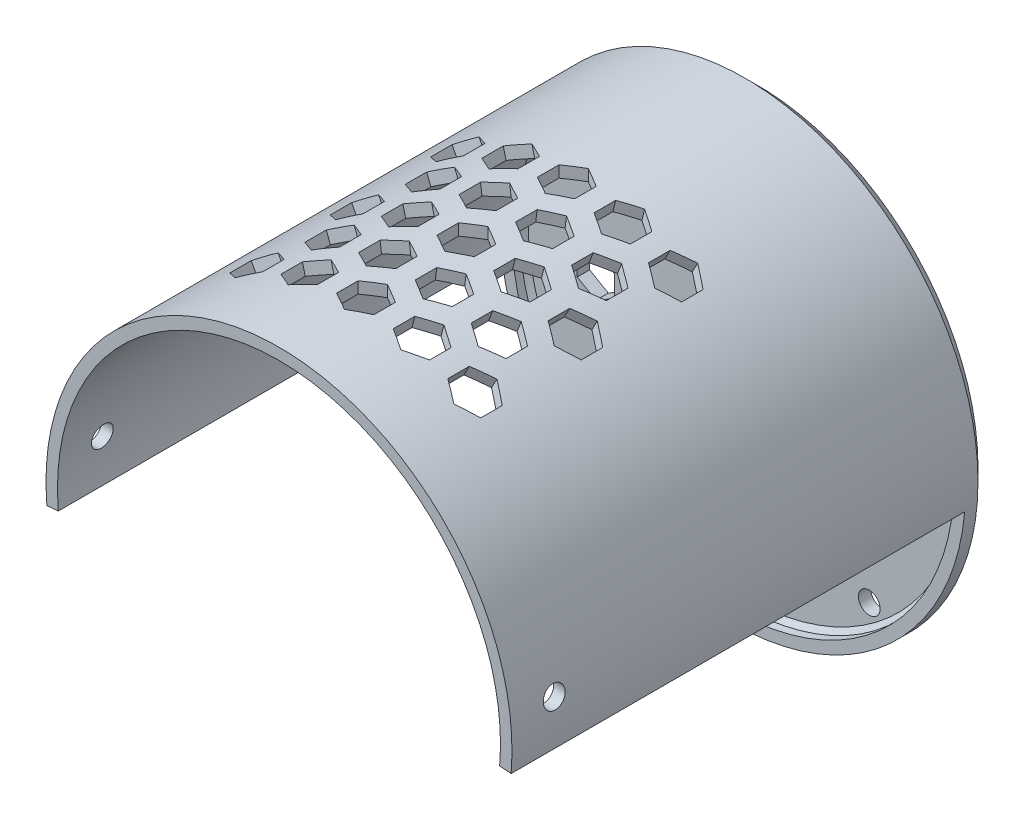
SolidWorks part; units mm, degrees
note: '?' marks a value the reader was unsure of.
material "PETG"
ref_plane "Спереди" through (0, 0, 0) normal (0, 0, 1) x (1, 0, 0)
ref_plane "Сверху" through (0, 0, 0) normal (0, 1, 0) x (1, 0, 0)
ref_plane "Справа" through (0, 0, 0) normal (1, 0, 0) x (0, 0, -1)
sketch "Эскиз1" plane through (0, 0, 0) normal (0, 0, 1) x (1, 0, 0)
  circle A0 centre (0, 0) radius 37.5
  dimension "D1" = 75
extrude "Бобышка-Вытянуть1" add sketch "Эскиз1" along normal blind 4
sketch "Эскиз2" plane through (0, 0, 4) normal (0, 0, 1) x (1, 0, 0)
  line L0 (-35.5143, -3.1071) -> (-37.3573, -3.2683)
  line L1 (0, 0) -> (-37.5, 0) construction
  line L2 (0, 0) -> (0, 22.5295) construction
  line L3 (35.5143, -3.1071) -> (37.3573, -3.2683)
  arc A0 (37.3573, -3.2683) -> (-37.3573, -3.2683) centre (0, 0) ccw
  arc A1 (35.5143, -3.1071) -> (-35.5143, -3.1071) centre (0, 0) ccw
  circle A2 centre (0, 0) radius 37.5 construction
  circle A3 centre (0, 0) radius 37.5 construction
  circle A4 centre (0, 0) radius 35.65 construction
  point P1 (55.8, 0)
  point P12 (54.9875, 16.8114)
  dimension "D1" = 1.85
  dimension "D2" = 5
extrude "Бобышка-Вытянуть2" add sketch "Эскиз2" along normal blind 73
chamfer "Фаска1" distance 2 angle 45 1 edges at (37.5, 0, 0)
sketch "Эскиз3" plane through (0, 0, 4) normal (0, 0, 1) x (1, 0, 0)
  circle A0 centre (0, 0) radius 35.65
  arc A1 (35.5143, -3.1071) -> (-35.5143, -3.1071) centre (0, 0) ccw construction
extrude "Вырез-Вытянуть1" cut sketch "Эскиз3" against normal blind 2
chamfer "Фаска2" distance 0.75 angle 45 1 edges at (35.65, 0, 2)
sketch "Эскиз4" plane through (0, 0, 0) normal (1, 0, 0) x (0, 0, -1)
  line L0 (-77, 37.5) -> (-77, -3.2683) construction
  line L1 (-77, -3.1071) -> (-4, -3.1071) construction
  circle A0 centre (-70, 3.8929) radius 1.75
  dimension "D1" = 3.5
  dimension "D2" = 7
  dimension "D3" = 7
extrude "Вырез-Вытянуть2" cut sketch "Эскиз4" against normal through all both and the other way through all
sketch "Эскиз5" plane through (0, 0, 0) normal (0, 0, -1) x (-1, 0, 0)
  line L0 (0, 0) -> (0, -32.5) construction
  circle A0 centre (0, 0) radius 32.5 construction
  circle A1 centre (-20, -25.6174) radius 1.75
  circle A2 centre (20, -25.6174) radius 1.75
  dimension "D1" = 65
  dimension "D2" = 3.5
  dimension "D3" = 40
extrude "Вырез-Вытянуть3" cut sketch "Эскиз5" against normal up to next
sketch "Эскиз6" plane through (0, 0, 0) normal (0, 0, -1) x (-1, 0, 0)
  line L0 (-16, -5.4641) -> (-13, -3.7321)
  line L1 (-24, -5.4641) -> (-21, -3.7321)
  line L2 (-21, -3.7321) -> (-21, -0.2679)
  line L3 (-21, -0.2679) -> (-24, 1.4641)
  line L4 (-24, 1.4641) -> (-27, -0.2679)
  line L5 (-27, -0.2679) -> (-27, -3.7321)
  line L6 (-27, -3.7321) -> (-24, -5.4641)
  line L7 (-13, -3.7321) -> (-13, -0.2679)
  line L8 (-13, -0.2679) -> (-16, 1.4641)
  line L9 (-16, 1.4641) -> (-19, -0.2679)
  line L10 (-19, -0.2679) -> (-19, -3.7321)
  line L11 (-19, -3.7321) -> (-16, -5.4641)
  line L12 (-8, -5.4641) -> (-5, -3.7321)
  line L13 (-5, -3.7321) -> (-5, -0.2679)
  line L14 (-5, -0.2679) -> (-8, 1.4641)
  line L15 (-8, 1.4641) -> (-11, -0.2679)
  line L16 (-11, -0.2679) -> (-11, -3.7321)
  line L17 (-11, -3.7321) -> (-8, -5.4641)
  line L18 (0, -5.4641) -> (3, -3.7321)
  line L19 (3, -3.7321) -> (3, -0.2679)
  line L20 (3, -0.2679) -> (0, 1.4641)
  line L21 (0, 1.4641) -> (-3, -0.2679)
  line L22 (-3, -0.2679) -> (-3, -3.7321)
  line L23 (-3, -3.7321) -> (0, -5.4641)
  line L24 (8, -5.4641) -> (11, -3.7321)
  line L25 (11, -3.7321) -> (11, -0.2679)
  line L26 (11, -0.2679) -> (8, 1.4641)
  line L27 (8, 1.4641) -> (5, -0.2679)
  line L28 (5, -0.2679) -> (5, -3.7321)
  line L29 (5, -3.7321) -> (8, -5.4641)
  line L30 (16, -5.4641) -> (19, -3.7321)
  line L31 (19, -3.7321) -> (19, -0.2679)
  line L32 (19, -0.2679) -> (16, 1.4641)
  line L33 (16, 1.4641) -> (13, -0.2679)
  line L34 (13, -0.2679) -> (13, -3.7321)
  line L35 (13, -3.7321) -> (16, -5.4641)
  line L36 (24, -5.4641) -> (27, -3.7321)
  line L37 (27, -3.7321) -> (27, -0.2679)
  line L38 (27, -0.2679) -> (24, 1.4641)
  line L39 (24, 1.4641) -> (21, -0.2679)
  line L40 (21, -0.2679) -> (21, -3.7321)
  line L41 (21, -3.7321) -> (24, -5.4641)
  line L42 (-16, -21.6241) -> (-13, -19.8921)
  line L43 (-13, -19.8921) -> (-13, -16.4279)
  line L44 (-13, -16.4279) -> (-16, -14.6959)
  line L45 (-16, -14.6959) -> (-19, -16.4279)
  line L46 (-19, -16.4279) -> (-19, -19.8921)
  line L47 (-19, -19.8921) -> (-16, -21.6241)
  line L48 (-8, -21.6241) -> (-5, -19.8921)
  line L49 (-5, -19.8921) -> (-5, -16.4279)
  line L50 (-5, -16.4279) -> (-8, -14.6959)
  line L51 (-8, -14.6959) -> (-11, -16.4279)
  line L52 (-11, -16.4279) -> (-11, -19.8921)
  line L53 (-11, -19.8921) -> (-8, -21.6241)
  line L54 (0, -21.6241) -> (3, -19.8921)
  line L55 (3, -19.8921) -> (3, -16.4279)
  line L56 (3, -16.4279) -> (0, -14.6959)
  line L57 (0, -14.6959) -> (-3, -16.4279)
  line L58 (-3, -16.4279) -> (-3, -19.8921)
  line L59 (-3, -19.8921) -> (0, -21.6241)
  line L60 (8, -21.6241) -> (11, -19.8921)
  line L61 (11, -19.8921) -> (11, -16.4279)
  line L62 (11, -16.4279) -> (8, -14.6959)
  line L63 (8, -14.6959) -> (5, -16.4279)
  line L64 (5, -16.4279) -> (5, -19.8921)
  line L65 (5, -19.8921) -> (8, -21.6241)
  line L66 (16, -21.6241) -> (19, -19.8921)
  line L67 (19, -19.8921) -> (19, -16.4279)
  line L68 (19, -16.4279) -> (16, -14.6959)
  line L69 (16, -14.6959) -> (13, -16.4279)
  line L70 (13, -16.4279) -> (13, -19.8921)
  line L71 (13, -19.8921) -> (16, -21.6241)
  line L72 (24, -21.6241) -> (27, -19.8921) [skipped]
  line L73 (27, -19.8921) -> (27, -16.4279) [skipped]
  line L74 (27, -16.4279) -> (24, -14.6959) [skipped]
  line L75 (24, -14.6959) -> (21, -16.4279) [skipped]
  line L76 (21, -16.4279) -> (21, -19.8921) [skipped]
  line L77 (21, -19.8921) -> (24, -21.6241) [skipped]
  line L78 (-24, -21.6241) -> (-21, -19.8921) [skipped]
  line L79 (-21, -19.8921) -> (-21, -16.4279) [skipped]
  line L80 (-21, -16.4279) -> (-24, -14.6959) [skipped]
  line L81 (-24, -14.6959) -> (-27, -16.4279) [skipped]
  line L82 (-27, -16.4279) -> (-27, -19.8921) [skipped]
  line L83 (-27, -19.8921) -> (-24, -21.6241) [skipped]
  line L84 (-21, -2) -> (-19, -2) construction
  line L85 (-20, -13.547) -> (-17, -11.815)
  line L86 (-17, -11.815) -> (-17, -8.3509)
  line L87 (-17, -8.3509) -> (-20, -6.6188)
  line L88 (-20, -6.6188) -> (-23, -8.3509)
  line L89 (-23, -8.3509) -> (-23, -11.815)
  line L90 (-23, -11.815) -> (-20, -13.547)
  line L91 (-20, -2) -> (-20, -10.0829) construction
  line L92 (-12, -13.547) -> (-9, -11.815)
  line L93 (-9, -11.815) -> (-9, -8.3509)
  line L94 (-9, -8.3509) -> (-12, -6.6188)
  line L95 (-12, -6.6188) -> (-15, -8.3509)
  line L96 (-15, -8.3509) -> (-15, -11.815)
  line L97 (-15, -11.815) -> (-12, -13.547)
  line L98 (-4, -13.547) -> (-1, -11.815)
  line L99 (-1, -11.815) -> (-1, -8.3509)
  line L100 (-1, -8.3509) -> (-4, -6.6188)
  line L101 (-4, -6.6188) -> (-7, -8.3509)
  line L102 (-7, -8.3509) -> (-7, -11.815)
  line L103 (-7, -11.815) -> (-4, -13.547)
  line L104 (4, -13.547) -> (7, -11.815)
  line L105 (7, -11.815) -> (7, -8.3509)
  line L106 (7, -8.3509) -> (4, -6.6188)
  line L107 (4, -6.6188) -> (1, -8.3509)
  line L108 (1, -8.3509) -> (1, -11.815)
  line L109 (1, -11.815) -> (4, -13.547)
  line L110 (12, -13.547) -> (15, -11.815)
  line L111 (15, -11.815) -> (15, -8.3509)
  line L112 (15, -8.3509) -> (12, -6.6188)
  line L113 (12, -6.6188) -> (9, -8.3509)
  line L114 (9, -8.3509) -> (9, -11.815)
  line L115 (9, -11.815) -> (12, -13.547)
  line L116 (20, -13.547) -> (23, -11.815)
  line L117 (23, -11.815) -> (23, -8.3509)
  line L118 (23, -8.3509) -> (20, -6.6188)
  line L119 (20, -6.6188) -> (17, -8.3509)
  line L120 (17, -8.3509) -> (17, -11.815)
  line L121 (17, -11.815) -> (20, -13.547)
  line L122 (-12, -29.707) -> (-9, -27.975) [skipped]
  line L123 (-9, -27.975) -> (-9, -24.5109) [skipped]
  line L124 (-9, -24.5109) -> (-12, -22.7788) [skipped]
  line L125 (-12, -22.7788) -> (-15, -24.5109) [skipped]
  line L126 (-15, -24.5109) -> (-15, -27.975) [skipped]
  line L127 (-15, -27.975) -> (-12, -29.707) [skipped]
  line L128 (-4, -29.707) -> (-1, -27.975)
  line L129 (-1, -27.975) -> (-1, -24.5109)
  line L130 (-1, -24.5109) -> (-4, -22.7788)
  line L131 (-4, -22.7788) -> (-7, -24.5109)
  line L132 (-7, -24.5109) -> (-7, -27.975)
  line L133 (-7, -27.975) -> (-4, -29.707)
  line L134 (4, -29.707) -> (7, -27.975)
  line L135 (7, -27.975) -> (7, -24.5109)
  line L136 (7, -24.5109) -> (4, -22.7788)
  line L137 (4, -22.7788) -> (1, -24.5109)
  line L138 (1, -24.5109) -> (1, -27.975)
  line L139 (1, -27.975) -> (4, -29.707)
  line L140 (12, -29.707) -> (15, -27.975) [skipped]
  line L141 (15, -27.975) -> (15, -24.5109) [skipped]
  line L142 (15, -24.5109) -> (12, -22.7788) [skipped]
  line L143 (12, -22.7788) -> (9, -24.5109) [skipped]
  line L144 (9, -24.5109) -> (9, -27.975) [skipped]
  line L145 (9, -27.975) -> (12, -29.707) [skipped]
  line L146 (20, -29.707) -> (23, -27.975) [skipped]
  line L147 (23, -27.975) -> (23, -24.5109) [skipped]
  line L148 (23, -24.5109) -> (20, -22.7788) [skipped]
  line L149 (20, -22.7788) -> (17, -24.5109) [skipped]
  line L150 (17, -24.5109) -> (17, -27.975) [skipped]
  line L151 (17, -27.975) -> (20, -29.707) [skipped]
  line L152 (-20, -29.707) -> (-17, -27.975) [skipped]
  line L153 (-17, -27.975) -> (-17, -24.5109) [skipped]
  line L154 (-17, -24.5109) -> (-20, -22.7788) [skipped]
  line L155 (-20, -22.7788) -> (-23, -24.5109) [skipped]
  line L156 (-23, -24.5109) -> (-23, -27.975) [skipped]
  line L157 (-23, -27.975) -> (-20, -29.707) [skipped]
  circle A0 centre (0, 0) radius 30 construction
  circle A1 centre (-24, -2) radius 3 construction
  circle A2 centre (-16, -2) radius 3 construction
  circle A3 centre (-8, -2) radius 3 construction
  circle A4 centre (0, -2) radius 3 construction
  circle A5 centre (8, -2) radius 3 construction
  circle A6 centre (16, -2) radius 3 construction
  circle A7 centre (24, -2) radius 3 construction
  circle A8 centre (-16, -18.16) radius 3 construction
  circle A9 centre (-8, -18.16) radius 3 construction
  circle A10 centre (0, -18.16) radius 3 construction
  circle A11 centre (8, -18.16) radius 3 construction
  circle A12 centre (16, -18.16) radius 3 construction
  circle A13 centre (24, -18.16) radius 3 construction
  circle A14 centre (-24, -18.16) radius 3 construction
  circle A15 centre (-20, -10.0829) radius 3 construction
  circle A16 centre (-12, -10.0829) radius 3 construction
  circle A17 centre (-4, -10.0829) radius 3 construction
  circle A18 centre (4, -10.0829) radius 3 construction
  circle A19 centre (12, -10.0829) radius 3 construction
  circle A20 centre (20, -10.0829) radius 3 construction
  circle A21 centre (-12, -26.2429) radius 3 construction
  circle A22 centre (-4, -26.2429) radius 3 construction
  circle A23 centre (4, -26.2429) radius 3 construction
  circle A24 centre (12, -26.2429) radius 3 construction
  circle A25 centre (20, -26.2429) radius 3 construction
  circle A26 centre (-20, -26.2429) radius 3 construction
  dimension "D1" = 60
  dimension "D2" = 6
  dimension "D3" = 2
  dimension "D4" = 24
  dimension "D11" = 8
  dimension "D7" = 3
  dimension "D8" = 8.0829
  dimension "D5" = 7
  dimension "D6" = 2
  dimension "D9" = 6
  dimension "D10" = 2
extrude "Вырез-Вытянуть4" cut sketch "Эскиз6" against normal up to next
sketch "Эскиз7" plane through (0, 0, 0) normal (0, 1, 0) x (1, 0, 0)
  line L0 (-37.5, -77) -> (37.5, -77) construction
  line L1 (0, -66.4641) -> (3, -64.7321)
  line L2 (3, -64.7321) -> (3, -61.2679)
  line L3 (3, -61.2679) -> (0, -59.5359)
  line L4 (0, -59.5359) -> (-3, -61.2679)
  line L5 (-3, -61.2679) -> (-3, -64.7321)
  line L6 (-3, -64.7321) -> (0, -66.4641)
  line L7 (0, -50.3041) -> (3, -48.5721)
  line L8 (3, -48.5721) -> (3, -45.1079)
  line L9 (3, -45.1079) -> (0, -43.3759)
  line L10 (0, -43.3759) -> (-3, -45.1079)
  line L11 (-3, -45.1079) -> (-3, -48.5721)
  line L12 (-3, -48.5721) -> (0, -50.3041)
  line L13 (0, -34.1441) -> (3, -32.4121)
  line L14 (3, -32.4121) -> (3, -28.9479)
  line L15 (3, -28.9479) -> (0, -27.2159)
  line L16 (0, -27.2159) -> (-3, -28.9479)
  line L17 (-3, -28.9479) -> (-3, -32.4121)
  line L18 (-3, -32.4121) -> (0, -34.1441)
  circle A0 centre (0, -63) radius 3 construction
  circle A1 centre (0, -46.84) radius 3 construction
  circle A2 centre (0, -30.68) radius 3 construction
  dimension "D1" = 6
  dimension "D2" = 14
  dimension "D3" = 3
extrude "Вырез-Вытянуть5" cut sketch "Эскиз7" along normal up to next
pattern_circular "Круговой массив1" count 3 every 14 about axis through (0, 0, 0) along (0, 0, 1) of "Вырез-Вытянуть5"
pattern_circular "Круговой массив2" count 3 every 14 about axis through (0, 0, 0) along (0, 0, 1) of "Вырез-Вытянуть5"
ref_axis "Ось1" through (0, 0, 77) along (0, 0, -1)?
ref_plane "Плоскость1" through (0, 0, 0) normal (-0.1219, 0.9925, 0) x (0, 0, -1)
sketch "Эскиз8" plane through (0, 0, 0) normal (-0.1219, 0.9925, 0) x (0, 0, -1)
  line L0 (-63, -1.5778) -> (-63, 1.5778) construction
  line L1 (-64.7321, -1.5778) -> (-61.2679, -1.5778) construction
  line L2 (-61.2679, 1.5778) -> (-64.7321, 1.5778) construction
  line L3 (-63, 0) -> (-54.92, 0) construction
  line L4 (-77, 0) -> (-4, 0) construction
  line L5 (-42.2241, 0) -> (-40.4921, -3)
  line L6 (-58.3841, 0) -> (-56.6521, -3)
  line L7 (-56.6521, -3) -> (-53.1879, -3)
  line L8 (-53.1879, -3) -> (-51.4559, 0)
  line L9 (-51.4559, 0) -> (-53.1879, 3)
  line L10 (-53.1879, 3) -> (-56.6521, 3)
  line L11 (-56.6521, 3) -> (-58.3841, 0)
  line L12 (-40.4921, -3) -> (-37.0279, -3)
  line L13 (-37.0279, -3) -> (-35.2959, 0)
  line L14 (-35.2959, 0) -> (-37.0279, 3)
  line L15 (-37.0279, 3) -> (-40.4921, 3)
  line L16 (-40.4921, 3) -> (-42.2241, 0)
  circle A0 centre (-54.92, 0) radius 3 construction
  circle A1 centre (-38.76, 0) radius 3 construction
  dimension "D1" = 6
  dimension "D2" = 8.08
  dimension "D3" = 2
extrude "Вырез-Вытянуть6" cut sketch "Эскиз8" along normal up to next
pattern_circular "Круговой массив3" count 3 every 14 about axis through (0, 0, 0) along (0, 0, 1) of "Вырез-Вытянуть6"
pattern_circular "Круговой массив4" count 2 every 14 about axis through (0, 0, 4) along (0, 0, -1) of "Вырез-Вытянуть6"
